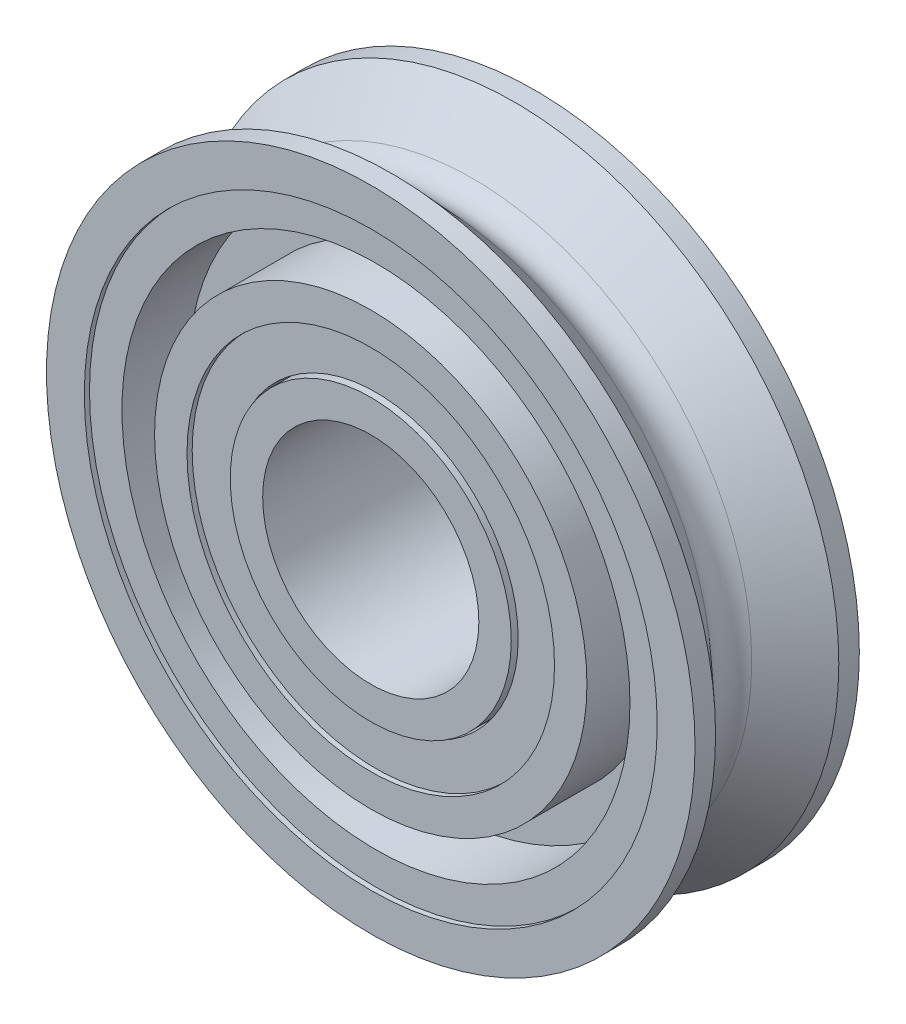
SolidWorks part; units mm, degrees
ref_plane "Front" through (0, 0, 0) normal (0, 0, 1) x (1, 0, 0)
ref_plane "Top" through (0, 0, 0) normal (0, 1, 0) x (1, 0, 0)
ref_plane "Right" through (0, 0, 0) normal (1, 0, 0) x (0, 0, -1)
sketch "Sketch1" plane through (0, 0, 0) normal (1, 0, 0) x (0, 0, -1)
  line L0 (0.9049, 4.7625) -> (1.2065, 4.7625)
  line L1 (-0.9049, 4.7625) -> (-1.2065, 4.7625)
  line L2 (-0.9049, 4.7625) -> (-0.292, 4.0968)
  line L3 (1.1303, 2.6987) -> (1.1303, 2.0638)
  line L4 (1.2065, 1.5875) -> (-1.2065, 1.5875)
  line L5 (-1.1303, 2.0638) -> (-1.1303, 2.6987)
  line L6 (0.9049, 4.7625) -> (0.292, 4.0968)
  line L7 (-1.2065, 4.2069) -> (-1.1303, 4.2069)
  line L8 (-1.2065, 0) -> (1.2065, 0) construction
  line L9 (-1.1303, 4.2069) -> (-1.1303, 3.7306)
  line L10 (1.2065, 4.7625) -> (1.2065, 4.2069)
  line L11 (1.2065, 4.2069) -> (1.1303, 4.2069)
  line L12 (-1.1303, 2.0638) -> (-1.2065, 2.0638)
  line L13 (-1.2065, 2.0638) -> (-1.2065, 1.5875)
  line L14 (0, 3.9688) -> (0, -3.9688) construction
  line L15 (1.2065, 2.0638) -> (1.1303, 2.0638)
  line L16 (1.2065, 2.0638) -> (1.2065, 1.5875)
  line L17 (-1.2065, 4.7625) -> (-1.2065, -4.7625) construction
  line L18 (-1.1303, 3.7306) -> (-0.1508, 3.7306)
  line L19 (-0.1508, 3.7306) -> (-0.1508, 3.175)
  line L20 (-0.1508, 3.175) -> (-1.2065, 3.175)
  line L21 (-1.2065, 4.2069) -> (-1.2065, 4.7625)
  line L22 (1.1303, 3.7306) -> (0.1508, 3.7306)
  line L23 (0.1508, 3.7306) -> (0.1508, 3.175)
  line L24 (0.1508, 3.175) -> (1.2065, 3.175)
  line L25 (1.1303, 4.2069) -> (1.1303, 3.7306)
  line L26 (-1.1303, 2.6987) -> (-1.2065, 2.6987)
  line L27 (-1.2065, 2.6987) -> (-1.2065, 3.175)
  line L28 (1.2065, 3.175) -> (1.2065, 2.6987)
  line L29 (1.2065, 2.6987) -> (1.1303, 2.6987)
  arc A0 (-0.292, 4.0968) -> (0.292, 4.0968) centre (0, 4.3656) ccw
  circle A1 centre (0, 4.3656) radius 0.3969 construction
  circle A2 centre (0, 0) radius 1.5875 construction
  circle A3 centre (0, 0) radius 2.0638 construction
  circle A4 centre (0, 0) radius 3.175 construction
  circle A5 centre (0, -4.3656) radius 0.3969 construction
  point P28 (-1.2065, 0)
  dimension "Rope Dia" = 0.7937
  dimension "Shaft Dia" = 3.175
  dimension "D1" = 4.1275
  dimension "D3" = 6.35
  dimension "Wd" = 2.413
  dimension "D8" = 0.3016
  dimension "Groove Dia" = 7.9375
  dimension "OD" = 9.525
  dimension "D6" = 0.0762
  dimension "D2" = 0.3016
revolve "Revolve1" add sketch "Sketch1" angle 360 about L8
sketch "Sketch2" plane through (0, 0, 0) normal (0, 0, 1) x (1, 0, 0)
  circle A0 centre (0, 0) radius 2.0638 construction
  circle A1 centre (0, 0) radius 2.0638
extrude "Cut-Extrude-Thin1" cut sketch "Sketch2" against normal through all and the other way through all thin thin type one direction wall 0.0254
ref_plane "Plane1" through (4.7625, 0, 0) normal (1, 0, 0) x (0, 0, -1)
ref_plane "Plane2" through (-4.7625, 0, 0) normal (1, 0, 0) x (0, 0, -1)
ref_axis "Axis1" through (4.7625, -5.2388, 0) along (0, 1, 0)
ref_axis "Axis2" through (-4.7625, -5.2388, 0) along (0, 1, 0)
equation "\"D1@Sketch1\" = \"Shaft Dia@Sketch1\" * 1.3"
equation "\"D3@Sketch1\" = \"Shaft Dia@Sketch1\" * 2"
equation "\"D8@Sketch1\" = \"Wd@Sketch1\" * .125"
equation "\"D2@Sketch1\" = \"D8@Sketch1\""
